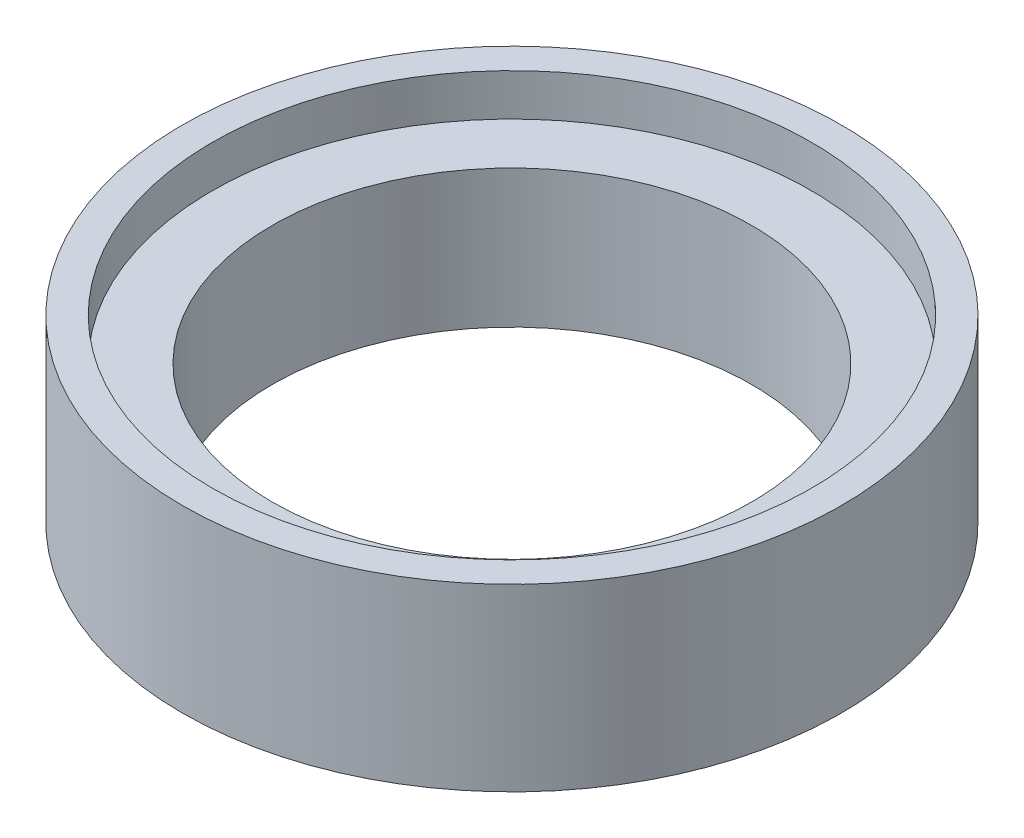
SolidWorks part; units mm, degrees
ref_plane "前视基准面" through (0, 0, 0) normal (0, 0, 1) x (1, 0, 0)
ref_plane "上视基准面" through (0, 0, 0) normal (0, 1, 0) x (1, 0, 0)
ref_plane "右视基准面" through (0, 0, 0) normal (1, 0, 0) x (0, 0, -1)
other "Configuration Table"
sketch "草图1" plane through (0, 0, 0) normal (0, 1, 0) x (1, 0, 0)
  circle A0 centre (0, 0) radius 5.5
  circle A1 centre (0, 0) radius 5
  circle A2 centre (0, 0) radius 4
  dimension "D1" = 11
  dimension "D2" = 10
  dimension "D3" = 8
extrude "凸台-拉伸1" add sketch "草图1" along normal blind 3 contours A0 A1 region at (-5.3444, 0, 0)
extrude "凸台-拉伸2" add sketch "草图1<3>" along normal blind 2.3 contours A1 A2 region at (-4.8586, 0, 0)
sketch "草图1<3>" plane through (0, 0, 0) normal (0, 1, 0) x (1, 0, 0) same geometry as "草图1"
